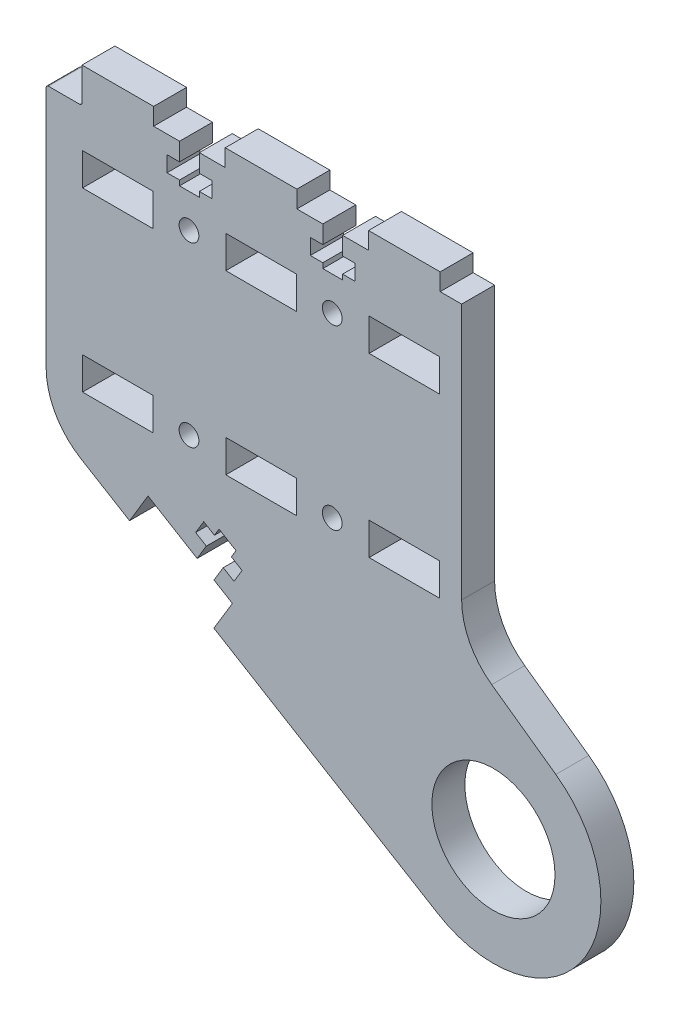
SolidWorks part; units mm, degrees
ref_plane "Front Plane" through (0, 0, 0) normal (0, 0, 1) x (1, 0, 0)
ref_plane "Top Plane" through (0, 0, 0) normal (0, 1, 0) x (1, 0, 0)
ref_plane "Right Plane" through (0, 0, 0) normal (1, 0, 0) x (0, 0, -1)
sketch "Sketch1" plane through (0, 0, 0) normal (0, 0, 1) x (1, 0, 0)
  line L0 (-38.0203, 0) -> (38.1796, 0) construction
  line L1 (31.7297, -12.8) -> (19.2297, -12.8)
  line L2 (38.1796, -12.8536) -> (38.1796, 12.8536)
  line L3 (31.7297, 12.8) -> (19.2297, 12.8)
  line L4 (-38.0203, -12.8) -> (-38.0203, 12.8)
  line L5 (38.1796, -12.8536) -> (-38.0203, 12.8) construction
  line L6 (38.1796, 12.8536) -> (-38.0203, -12.8) construction
  line L7 (6.3297, 18.542) -> (-6.1703, 18.542)
  line L8 (-19.0703, -18.542) -> (-31.5703, -12.8) construction
  line L9 (-19.0703, -12.8) -> (-31.5703, -18.542) construction
  line L10 (6.3297, -12.8) -> (-6.1703, -12.8)
  line L11 (-19.0703, -12.8) -> (-31.5703, -12.8)
  line L12 (31.7297, -12.8) -> (31.7297, -18.542)
  line L13 (19.2297, -12.8) -> (19.2297, -18.542)
  line L14 (38.1796, 28.575) -> (31.8297, 28.575)
  line L15 (-19.0703, 12.8) -> (-19.0703, 18.542)
  line L16 (-19.0703, 18.542) -> (-31.5703, 18.542)
  line L17 (-31.5703, 12.8) -> (-31.5703, 18.542)
  line L18 (-19.0703, 12.8) -> (-31.5703, 18.542) construction
  line L19 (-19.0703, 18.542) -> (-31.5703, 12.8) construction
  line L20 (-6.1703, 12.8) -> (-6.1703, 18.542)
  line L21 (6.3297, 12.8) -> (6.3297, 18.542)
  line L22 (31.7297, 18.542) -> (19.2297, 18.542)
  line L23 (19.2297, 12.8) -> (19.2297, 18.542)
  line L24 (31.7297, 12.8) -> (31.7297, 18.542)
  line L25 (-19.0703, 12.8) -> (-31.5703, 12.8)
  line L26 (6.3297, 12.8) -> (-6.1703, 12.8)
  line L27 (-38.0203, 12.8) -> (-38.0203, 28.575)
  line L28 (0.0797, 0) -> (0.0797, 28.575) construction
  line L29 (11.0271, 28.575) -> (6.4297, 28.575)
  line L30 (38.1796, 28.575) -> (38.1796, 12.8536)
  line L31 (31.7297, -18.542) -> (19.2297, -18.542)
  line L32 (6.3297, -12.8) -> (6.3297, -18.542)
  line L33 (-6.1703, -12.8) -> (-6.1703, -18.542)
  line L34 (-31.5703, -12.8) -> (-31.5703, -18.542)
  line L35 (-19.0703, -18.542) -> (-31.5703, -18.542)
  line L36 (-19.0703, -12.8) -> (-19.0703, -18.542)
  line L37 (6.3297, -18.542) -> (-6.1703, -18.542)
  line L38 (31.7297, -12.8) -> (19.2297, -12.8)
  line L39 (-19.0703, -12.8) -> (-31.5703, -12.8)
  line L40 (6.3297, -12.8) -> (-6.1703, -12.8)
  line L41 (6.3297, 12.8) -> (19.2297, 12.8) construction
  line L42 (-38.0203, -25.196) -> (31.432, -67.11)
  line L43 (38.1796, -25.196) -> (52.3348, -35.2893)
  line L44 (-10.8677, 22.1694) -> (-14.3729, 22.1694) construction
  line L45 (-8.6516, 24.0109) -> (-16.5891, 24.0109) construction
  line L46 (-10.8677, 26.9875) -> (-14.3729, 26.9875) construction
  line L47 (-12.6203, 28.575) -> (-12.6203, 24.5335) construction
  line L48 (-6.1703, 12.8) -> (-19.0703, 12.8) construction
  line L49 (-14.3729, 21.717) -> (-14.3729, 22.6219)
  line L50 (12.7797, 0) -> (12.7797, 28.575) construction
  line L51 (14.5323, 25.4) -> (16.7484, 25.4)
  line L52 (14.5323, 22.6219) -> (16.7484, 22.6219)
  line L53 (11.0271, 25.4) -> (11.0271, 28.575)
  line L54 (-10.8677, 21.717) -> (-10.8677, 22.6219)
  line L55 (-38.0203, -12.8) -> (-38.0203, -25.196)
  line L56 (14.5323, 25.4) -> (14.5323, 28.575)
  line L57 (12.7797, 28.575) -> (12.7797, 24.5335) construction
  line L58 (38.1796, -12.8536) -> (38.1796, -25.196)
  line L59 (11.0271, 26.9875) -> (14.5323, 26.9875) construction
  line L60 (8.8109, 22.6219) -> (11.0271, 22.6219)
  line L61 (8.8109, 22.6219) -> (8.8109, 25.4)
  line L62 (8.8109, 25.4) -> (11.0271, 25.4)
  line L63 (16.7484, 22.6219) -> (16.7484, 25.4)
  line L64 (12.7797, 24.5335) -> (12.7797, 20.1202) construction
  line L65 (8.8109, 24.0109) -> (16.7484, 24.0109) construction
  line L66 (11.0271, 21.717) -> (14.5323, 21.717)
  line L67 (11.0271, 21.717) -> (11.0271, 22.6219)
  line L68 (-6.2703, 28.575) -> (-10.8677, 28.575)
  line L69 (14.5323, 21.717) -> (14.5323, 22.6219)
  line L70 (12.7797, 20.1202) -> (12.7797, 21.717) construction
  line L71 (11.0271, 22.1694) -> (14.5323, 22.1694) construction
  line L72 (-10.8677, 21.717) -> (-14.3729, 21.717)
  line L73 (-16.5891, 22.6219) -> (-16.5891, 25.4)
  line L74 (-8.6516, 25.4) -> (-10.8677, 25.4)
  line L75 (-8.6516, 22.6219) -> (-8.6516, 25.4)
  line L76 (-8.6516, 22.6219) -> (-10.8677, 22.6219)
  line L77 (-14.3729, 25.4) -> (-14.3729, 28.575)
  line L78 (-10.8677, 25.4) -> (-10.8677, 28.575)
  line L79 (-14.3729, 22.6219) -> (-16.5891, 22.6219)
  line L80 (-14.3729, 25.4) -> (-16.5891, 25.4)
  line L81 (-14.3729, 28.575) -> (-18.9703, 28.575)
  line L82 (19.1297, 31.623) -> (19.1297, 28.575)
  line L83 (-6.2703, 31.623) -> (6.4297, 31.623)
  line L84 (-6.2703, 31.623) -> (-6.2703, 28.575)
  line L85 (31.8297, 31.623) -> (31.8297, 28.575)
  line L86 (6.4297, 31.623) -> (6.4297, 28.575)
  line L87 (0.0797, 28.575) -> (0.0797, 31.623) construction
  line L88 (-6.2703, 30.099) -> (6.4297, 30.099) construction
  line L89 (31.8297, 30.099) -> (19.1297, 30.099) construction
  line L90 (31.8297, 31.623) -> (19.1297, 31.623)
  line L91 (19.1297, 28.575) -> (14.5323, 28.575)
  line L92 (-18.9703, 31.623) -> (-18.9703, 28.575)
  line L93 (-31.6703, 31.623) -> (-18.9703, 31.623)
  line L94 (-31.6703, 30.099) -> (-18.9703, 30.099) construction
  line L95 (-31.6703, 31.623) -> (-31.6703, 28.575)
  line L96 (-31.6703, 28.575) -> (-38.0203, 28.575)
  arc A0 (31.432, -67.11) -> (52.3348, -35.2893) centre (41.275, -50.8) ccw
  circle A1 centre (12.7, 15.721) radius 1.7526
  circle A2 centre (-12.7, 15.721) radius 1.7526
  circle A3 centre (12.7, -15.721) radius 1.7526
  circle A4 centre (-12.7, -15.721) radius 1.7526
  circle A6 centre (41.275, -50.8) radius 10.9125
  point P0 (0, 0)
  point P8 (-25.3203, 15.671)
  point P16 (12.7, 30.1625)
  point P37 (-25.3203, -15.671)
  point P55 (12.7797, 26.9875)
  point P59 (12.7797, 24.0109)
  point P60 (-0.4211, 99.3522)
  point P62 (-25.6211, 23.1522)
  point P65 (12.7797, 22.1694)
  point P70 (-3.225, -28.575)
  point P73 (12.7797, 24.0109)
  point P91 (-12.6203, 24.0109)
  point P92 (-12.6203, 22.1694)
  point P97 (-12.6203, 26.9875)
  point P98 (-12.5407, 30.1625)
  point P99 (0.0797, 30.099)
  point P117 (25.4797, 30.099)
  point P120 (-25.3203, 30.099)
  dimension "D3" = 12.5
  dimension "D5" = 50.8
  dimension "D6" = 41.275
  dimension "D8" = 12.7
  dimension "D13" = 3.5052
  dimension "D11" = 28.575
  dimension "D19" = 21.825
  dimension "D7" = 38.1
  dimension "D1" = 25.6
  dimension "D2" = 76.2
  dimension "D4" = 5.742
  dimension "D9" = 12.7
  dimension "D10" = 3
  dimension "D12" = 2.921
  dimension "D14" = 2.921
  dimension "D15" = 15.721
  dimension "D16" = 12.7
  dimension "D17" = 3.048
  dimension "D20" = 9.525
  dimension "D21" = 9.525
  dimension "D18" = 12.7
  dimension "D22" = 3.5052
  dimension "D23" = 2.7781
  dimension "D24" = 7.9375
  dimension "D25" = 3.175
  dimension "D26" = 0.9049
extrude "Boss-Extrude1" add sketch "Sketch1" along normal blind 5.842 contours L58 L2 L30 L27 L4 L55 A4 L32 L37 L33 L10 L11 L36 L35 L34 L12 L31 L13 L1 L21 L26 L20 L7 L15 L25 L17 L16 L24 L3 L23 L22 region at (7.1681, -13.709, 0)
fillet "Fillet1" [suppressed] radius 3.175
fillet "Fillet2" [suppressed] radius 3.175
fillet "Fillet3" [suppressed] radius 3.175
sketch "Sketch3" [suppressed] plane through (0, 0, 5.842) normal (0, 0, 1) x (1, 0, 0)
  line L0 (12.6, 94.996) -> (12.7, -15.721) construction
  circle A0 centre (12.7147, -32.004) radius 2.413
  dimension "D1" = 4.826
  dimension "D2" = 127
extrude "Cut-Extrude2" [suppressed] cut sketch "Sketch3" against normal through all
sketch "Sketch5" [suppressed] plane through (0, 0, 5.842) normal (0, 0, 1) x (1, 0, 0)
  line L1 (-55.0734, 111.0269) -> (34.825, 111.0269)
  line L2 (-55.0734, 111.0269) -> (-55.0734, 25.146)
  line L3 (-55.0734, 25.146) -> (34.825, 25.146)
  line L4 (34.825, 111.0269) -> (34.825, 25.146)
extrude "Cut-Extrude3" [suppressed] cut sketch "Sketch5" against normal through all
sketch "Sketch6" [suppressed] plane through (0, 0, 5.842) normal (0, 0, 1) x (1, 0, 0)
  line L0 (-34.925, 25.146) -> (-33.9441, 25.146) construction
  line L1 (31.4879, 25.146) -> (-22.4871, 25.146)
  line L2 (31.4879, 78.486) -> (34.6629, 74.676)
  line L3 (31.4879, 78.486) -> (-20.5821, 78.486)
  line L4 (-22.4871, 25.146) -> (-25.0279, 25.146)
  line L5 (34.6629, 25.146) -> (-22.4871, 78.486) construction
  line L6 (34.6629, 78.486) -> (-22.4871, 25.146) construction
  line L7 (6.0879, 25.146) -> (6.0879, 48.411) construction
  line L8 (-31.75, 25.146) -> (-22.4871, 51.816)
  line L9 (-38.1, -25.146) -> (-38.1, 25.4) construction
  line L10 (34.6629, 74.676) -> (34.6629, 41.021)
  line L11 (-31.75, 25.146) -> (-25.0279, 25.146)
  line L12 (-22.4871, 51.816) -> (-22.4871, 71.3764)
  line L13 (31.4879, 70.866) -> (31.4879, 42.926) construction
  line L14 (31.4879, 37.846) -> (31.4879, 25.146)
  line L15 (31.4879, 37.846) -> (34.6629, 41.021)
  circle A0 centre (31.4879, 70.866) radius 1.651
  circle A1 centre (31.4879, 42.926) radius 1.651
  circle A2 centre (-20.5821, 74.676) radius 1.651
  circle A3 centre (-19.3121, 27.686) radius 1.651
  arc A4 (-20.5821, 78.486) -> (-22.4871, 71.3764) centre (-20.5821, 74.676) ccw
  point P0 (6.0879, 51.816)
  point P13 (-25.7515, 23.0626)
  point P14 (-16.4886, 49.7326)
  dimension "D5" = 3.302
  dimension "D6" = 3.302
  dimension "D9" = 12.7
  dimension "D10" = 3.302
  dimension "D12" = 3.302
  dimension "D1" = 53.34
  dimension "D2" = 57.15
  dimension "D3" = 6.35
  dimension "D7" = 49.53
  dimension "D8" = 27.94
  dimension "D11" = 52.07
  dimension "D13" = 50.8
  dimension "D14" = 15.24
  dimension "D4" = 7.62
extrude "Boss-Extrude3" [suppressed] add sketch "Sketch6" against normal up to surface (5.842 mm away) up to face at (52.1875, -50.8, 0)
fillet "Fillet6" [suppressed] radius 3.175
fillet "Fillet7" [suppressed] radius 1.5875
sketch "Sketch7" [suppressed] plane through (0, 0, 5.842) normal (0, 0, 1) x (1, 0, 0)
  line L0 (20.9561, 53.086) -> (-41.1495, 53.086) construction
  line L2 (5.0811, 78.486) -> (5.0811, 25.1147) construction
  line L3 (30.7443, 78.486) -> (-20.5821, 78.486) construction
  line L4 (5.0811, 65.786) -> (5.0811, 40.386) construction
  line L5 (8.2561, 65.786) -> (8.2561, 40.386)
  line L6 (1.9061, 65.786) -> (1.9061, 40.386)
  line L7 (17.7811, 65.786) -> (17.7811, 40.386) construction
  line L8 (20.9561, 65.786) -> (20.9561, 40.386)
  line L9 (14.6061, 65.786) -> (14.6061, 40.386)
  line L10 (-24.5007, 53.086) -> (20.9561, 53.086) construction
  line L11 (-7.6189, 65.786) -> (-7.6189, 40.386) construction
  line L12 (-10.7939, 65.786) -> (-10.7939, 40.386)
  line L13 (-4.4439, 65.786) -> (-4.4439, 40.386)
  arc A0 (8.2561, 65.786) -> (1.9061, 65.786) centre (5.0811, 65.786) ccw
  arc A1 (1.9061, 40.386) -> (8.2561, 40.386) centre (5.0811, 40.386) ccw
  arc A2 (20.9561, 65.786) -> (14.6061, 65.786) centre (17.7811, 65.786) ccw
  arc A3 (14.6061, 40.386) -> (20.9561, 40.386) centre (17.7811, 40.386) ccw
  arc A4 (-10.7939, 65.786) -> (-4.4439, 65.786) centre (-7.6189, 65.786) cw
  arc A5 (-4.4439, 40.386) -> (-10.7939, 40.386) centre (-7.6189, 40.386) cw
  point P10 (5.0811, 53.086)
  point P18 (17.7811, 53.086)
  point P26 (-7.6189, 53.086)
  dimension "D2" = 3.175
  dimension "D1" = 25.4
  dimension "D3" = 25.4
  dimension "D4" = 2
extrude "Cut-Extrude4" [suppressed] cut sketch "Sketch7" against normal through all
sketch "Sketch9" [suppressed] plane through (0, 0, 5.842) normal (0, 0, 1) x (1, 0, 0)
  line L0 (-38.1, -7.52) -> (38.1, -7.52) construction
  line L1 (-38.1, -25.146) -> (-38.1, 21.971) construction
  line L2 (38.1, 21.971) -> (38.1, -25.146) construction
  line L3 (-19.15, 12.8) -> (-31.65, 12.8) construction
  text T0 "SERGE" font "Roboto Condensed" height in points 42
  dimension "D1" = 20.32
extrude "Cut-Extrude5" [suppressed] cut sketch "Sketch9" against normal blind 0.3969
sketch "Sketch10" [suppressed] plane through (0, 0, 5.842) normal (0, 0, 1) x (1, 0, 0)
  line L0 (-38.1, -4.345) -> (38.1, -4.345) construction
  line L1 (-38.1, -25.146) -> (-38.1, 21.971) construction
  line L2 (38.1, 21.971) -> (38.1, -25.146) construction
  line L3 (-19.15, 12.8) -> (-31.65, 12.8) construction
  text T0 "SERGE" font "Bebas Neue" height in points 36
  dimension "D1" = 17.145
extrude "Cut-Extrude6" [suppressed] cut sketch "Sketch10" against normal blind 0.1984
sketch "Sketch11" [suppressed] plane through (0, 0, 5.842) normal (0, 0, 1) x (1, 0, 0)
  line L0 (12.6, 94.996) -> (12.7, 15.721) construction
  line L1 (9.467, 61.7085) -> (15.817, 61.7085) construction
  line L2 (9.467, 63.296) -> (15.817, 63.296)
  line L3 (9.467, 60.121) -> (15.817, 60.121)
  line L4 (31.75, 55.3585) -> (-6.45, 55.3585) construction
  line L5 (-6.45, 61.4095) -> (-6.45, 28.321) construction
  line L6 (9.4508, 74.4085) -> (15.8008, 74.4085) construction
  line L7 (9.4508, 75.996) -> (15.8008, 75.996)
  line L8 (9.4508, 72.821) -> (15.8008, 72.821)
  line L9 (9.4345, 87.1085) -> (15.7845, 87.1085) construction
  line L10 (9.4345, 88.696) -> (15.7845, 88.696)
  line L11 (9.4345, 85.521) -> (15.7845, 85.521)
  line L12 (9.4345, 23.6085) -> (15.7845, 23.6085) construction
  line L13 (9.4345, 22.021) -> (15.7845, 22.021)
  line L14 (9.4345, 25.196) -> (15.7845, 25.196)
  line L15 (9.4508, 36.3085) -> (15.8008, 36.3085) construction
  line L16 (9.4508, 34.721) -> (15.8008, 34.721)
  line L17 (9.4508, 37.896) -> (15.8008, 37.896)
  line L18 (9.467, 49.0085) -> (15.817, 49.0085) construction
  line L19 (9.467, 47.421) -> (15.817, 47.421)
  line L20 (9.467, 50.596) -> (15.817, 50.596)
  arc A0 (9.467, 63.296) -> (9.467, 60.121) centre (9.467, 61.7085) ccw
  arc A1 (15.817, 60.121) -> (15.817, 63.296) centre (15.817, 61.7085) ccw
  arc A2 (9.4508, 75.996) -> (9.4508, 72.821) centre (9.4508, 74.4085) ccw
  arc A3 (15.8008, 72.821) -> (15.8008, 75.996) centre (15.8008, 74.4085) ccw
  arc A4 (9.4345, 88.696) -> (9.4345, 85.521) centre (9.4345, 87.1085) ccw
  arc A5 (15.7845, 85.521) -> (15.7845, 88.696) centre (15.7845, 87.1085) ccw
  arc A6 (9.4345, 22.021) -> (9.4345, 25.196) centre (9.4345, 23.6085) cw
  arc A7 (15.7845, 25.196) -> (15.7845, 22.021) centre (15.7845, 23.6085) cw
  arc A8 (9.4508, 34.721) -> (9.4508, 37.896) centre (9.4508, 36.3085) cw
  arc A9 (15.8008, 37.896) -> (15.8008, 34.721) centre (15.8008, 36.3085) cw
  arc A10 (9.467, 47.421) -> (9.467, 50.596) centre (9.467, 49.0085) cw
  arc A11 (15.817, 50.596) -> (15.817, 47.421) centre (15.817, 49.0085) cw
  point P6 (12.642, 61.7085)
  point P16 (12.65, 55.3585)
  point P19 (12.6258, 74.4085)
  point P26 (12.6095, 87.1085)
  point P32 (12.6095, 23.6085)
  point P39 (12.6258, 36.3085)
  point P46 (12.642, 49.0085)
  dimension "D1" = 1.5875
  dimension "D2" = 6.35
  dimension "D3" = 6.35
  dimension "D4" = 3
extrude "Cut-Extrude7" [suppressed] cut sketch "Sketch11" against normal through all
fillet "Fillet8" [suppressed] radius 25.4
fillet "Fillet10" radius 12.7 1 edges at (-38.0203, -25.196, 2.921)
fillet "Fillet11" radius 12.7 1 edges at (38.1796, -25.196, 2.921)
sketch "Sketch12" [suppressed] plane through (0, 0, 5.842) normal (0, 0, 1) x (1, 0, 0)
  line L1 (-59.2155, 110.7085) -> (34.825, 110.7085)
  line L2 (-59.2155, 110.7085) -> (-59.2155, 25.146)
  line L3 (-59.2155, 25.146) -> (34.825, 25.146)
  line L4 (34.825, 110.7085) -> (34.825, 25.146)
  line L5 (-59.2155, 110.7085) -> (34.825, 25.146) construction
  line L6 (-59.2155, 25.146) -> (34.825, 110.7085) construction
  arc A0 (31.65, 28.321) -> (34.825, 25.146) centre (34.825, 28.321) ccw construction
  point P4 (-12.1952, 67.9272)
sketch "Sketch16" plane through (0, 0, 0) normal (0, 0, -1) x (-1, 0, 0)
  line L0 (-35.6396, 28.575) -> (-35.6396, -23.3849)
  line L1 (-38.1796, 28.575) -> (-31.8297, 28.575) construction
  line L2 (-35.6396, -23.3849) -> (-43.5064, -28.9942)
  line L3 (-43.5064, -28.9942) -> (-52.3348, -35.2893) construction
  line L4 (-38.1796, 28.575) -> (-38.1796, -18.6537) construction
  line L5 (-38.1796, 28.575) -> (-35.6396, 28.575)
  line L6 (-38.1796, 28.575) -> (-38.1796, -18.6537)
  arc A0 (-43.5064, -28.9942) -> (-38.1796, -18.6537) centre (-50.8796, -18.6537) ccw construction
  arc A1 (-43.5064, -28.9942) -> (-38.1796, -18.6537) centre (-50.8796, -18.6537) ccw
  dimension "D1" = 2.54
extrude "Cut-Extrude9" cut sketch "Sketch16" against normal through all
fillet "Fillet12" radius 12.7 1 edges at (35.6396, -23.3849, 2.921)
sketch "Sketch17" plane through (0, 0, 5.842) normal (0, 0, 1) x (1, 0, 0)
  line L0 (-31.6703, 28.575) -> (-38.0203, 28.575) construction
  line L1 (-31.6703, 28.575) -> (-38.0203, 28.575)
  line L2 (-31.6703, 28.575) -> (-31.6703, 25.4)
  line L3 (-31.6703, 25.4) -> (-38.0203, 25.4)
  line L4 (-38.0203, 28.575) -> (-38.0203, 25.4)
  line L5 (-38.0203, -18.0269) -> (-38.0203, 28.575) construction
  dimension "D1" = 3.175
extrude "Cut-Extrude10" cut sketch "Sketch17" against normal through all
fillet "Fillet13" radius 0.4 2 edges at (-38.0203, 25.4, 2.921) (-31.6703, 25.4, 2.921)
sketch "Sketch18" plane through (0, 0, 5.842) normal (0, 0, 1) x (1, 0, 0)
  line L0 (-23.2347, -34.1191) -> (-8.2838, -43.1418)
  line L1 (-23.2347, -34.1191) -> (-19.9537, -28.6824)
  line L2 (-8.2838, -43.1418) -> (-5.0028, -37.7051)
  line L3 (-19.9537, -28.6824) -> (-11.2604, -33.9287)
  line L4 (-31.8823, -28.9002) -> (31.432, -67.11) construction
  line L5 (-31.5703, -12.8) -> (-31.5703, -18.542) construction
  line L6 (-6.6433, -40.4235) -> (-21.5942, -31.4007) construction
  line L8 (-9.7599, -34.8343) -> (-1.8729, -21.7654) construction
  line L9 (-9.6199, -31.2104) -> (-11.2604, -33.9287)
  line L10 (-8.2594, -35.7398) -> (-5.0028, -37.7051)
  line L12 (-6.6189, -33.0215) -> (-8.2594, -35.7398)
  line L13 (-9.6199, -31.2104) -> (-8.2594, -35.7398) construction
  line L14 (-11.2604, -33.9287) -> (-6.6189, -33.0215) construction
  line L15 (-11.5173, -30.0653) -> (-9.6199, -31.2104)
  line L16 (-11.5173, -30.0653) -> (-10.0819, -27.6867)
  line L17 (-4.7215, -34.1665) -> (-3.286, -31.788)
  line L18 (-10.0819, -27.6867) -> (-8.1845, -28.8318)
  line L19 (-11.5173, -30.0653) -> (-3.286, -31.788) construction
  line L20 (-4.7215, -34.1665) -> (-10.0819, -27.6867) construction
  line L21 (-7.3642, -27.4726) -> (-8.1845, -28.8318)
  line L22 (-7.3642, -27.4726) -> (-4.3632, -29.2838)
  line L23 (-6.6189, -33.0215) -> (-4.7215, -34.1665)
  line L24 (-4.3632, -29.2838) -> (-5.1834, -30.6429)
  line L25 (-7.3642, -27.4726) -> (-5.1834, -30.6429) construction
  line L26 (-8.1845, -28.8318) -> (-4.3632, -29.2838) construction
  line L27 (-5.1834, -30.6429) -> (-3.286, -31.788)
  point P7 (-31.5703, -15.671)
  point P15 (-8.9396, -33.4751)
  point P16 (-7.4017, -30.9266)
  point P21 (-6.2738, -29.0578)
  point P32 (-14.1187, -35.9121)
  dimension "D1" = 17.4625
  dimension "D2" = 6.35
  dimension "D3" = 28.575
  dimension "D4" = 3.5052
  dimension "D5" = 3.175
  dimension "D6" = 7.9375
  dimension "D7" = 2.7781
  dimension "D8" = 3.5052
  dimension "D9" = 1.5875
  dimension "D10" = 3.175
extrude "Cut-Extrude11" cut sketch "Sketch18" against normal through all
